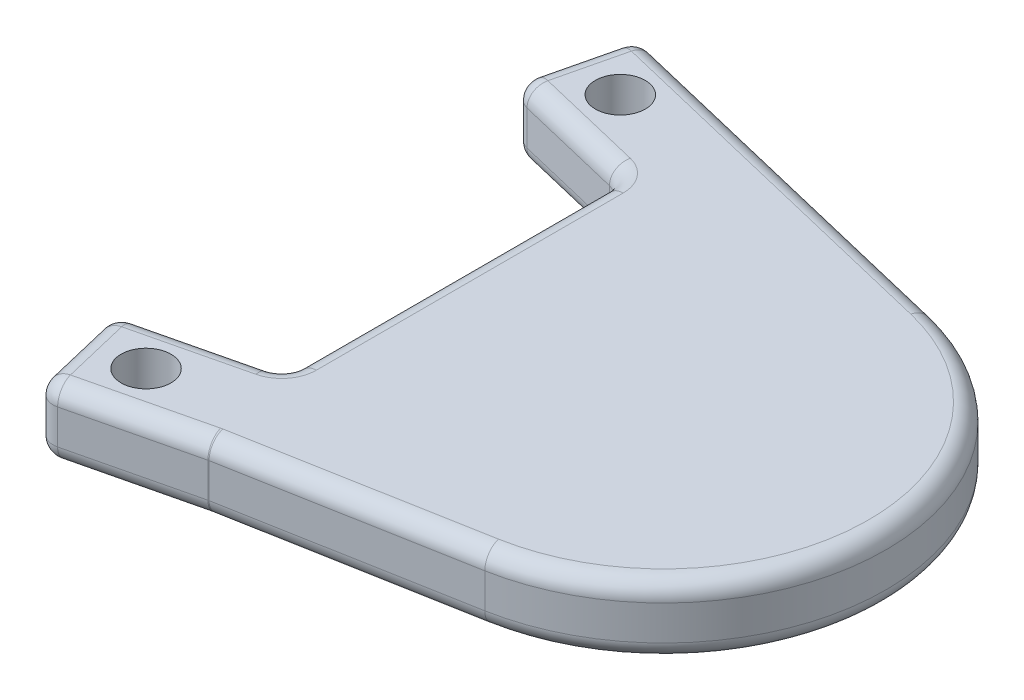
SolidWorks part; units mm, degrees
ref_plane "Front Plane" through (0, 0, 0) normal (0, 0, 1) x (1, 0, 0)
ref_plane "Top Plane" through (0, 0, 0) normal (0, 1, 0) x (1, 0, 0)
ref_plane "Right Plane" through (0, 0, 0) normal (1, 0, 0) x (0, 0, -1)
sketch "Sketch1" plane through (0, 0, 0) normal (0, 1, 0) x (1, 0, 0)
  line L0 (20.1768, -12.5857) -> (55.4095, -21.0327)
  line L7 (30.6561, -55.5343) -> (30.6561, -24.893)
  line L8 (30.6561, -24.893) -> (17.9561, -21.8482)
  line L9 (17.9561, -21.8482) -> (20.1768, -12.5857)
  line L11 (20.1768, -67.8416) -> (32.8768, -64.7968)
  line L12 (32.8768, -64.7968) -> (54.307, -60.8969)
  line L13 (30.6561, -55.5343) -> (17.9561, -58.5791)
  line L14 (-49.0101, -74.6341) -> (30.0474, -55.6802) construction
  line L15 (17.9561, -58.5791) -> (20.1768, -67.8416)
  line L16 (50.6586, -60.5337) -> (-49.8976, -84.6418) construction
  line L25 (30.6561, -54.9083) -> (30.6561, -25.519) construction
  line L26 (30.0474, -24.7471) -> (-49.0101, -5.7932) construction
  line L29 (-49.8976, 4.2145) -> (29.6773, -14.8634) construction
  arc A0 (54.307, -60.8969) -> (55.4095, -21.0327) centre (50.6586, -40.8487) ccw
  dimension "D1" = 12.7
  dimension "D3" = 12.7
extrude "Boss-Extrude1" add sketch "Sketch1" along normal blind 6.35
sketch "Sketch2" plane through (0, 6.35, 0) normal (0, 1, 0) x (1, 0, 0)
  line L0 (30.6561, -24.893) -> (30.6561, -55.5343) construction
  line L1 (20.1768, -67.8416) -> (32.8768, -64.7968) construction
  line L2 (24.3061, -61.9541) -> (25.4165, -66.5854) construction
  line L4 (24.3061, -61.9541) -> (23.1958, -57.3229) construction
  line L5 (30.6561, -55.5343) -> (17.9561, -58.5791) construction
  line L6 (24.3061, -18.4732) -> (23.1958, -23.1044) construction
  line L7 (17.9561, -21.8482) -> (30.6561, -24.893) construction
  line L8 (24.3061, -18.4732) -> (25.4165, -13.8419) construction
  line L9 (55.4095, -21.0327) -> (20.1768, -12.5857) construction
  line L10 (55.4095, -21.0327) -> (20.1768, -12.5857) construction
  circle A10 centre (24.3061, -61.9541) radius 2.286
  circle A11 centre (24.3061, -18.4732) radius 2.286
  dimension "D1" = 6.35
  dimension "D4" = 4.572
  dimension "D2" = 6.35
extrude "Cut-Extrude1" cut sketch "Sketch2" against normal through all
sketch "Sketch5" plane through (0, 0, 0) normal (0, -1, 0) x (1, 0, 0)
  line L0 (50.6586, 40.8432) -> (57.8976, 40.8432) construction
  line L1 (50.6586, 48.0877) -> (50.6586, 40.8432) construction
  circle A0 centre (50.6586, 40.8432) radius 2.286
  circle A1 centre (50.6586, 40.8487) radius 7.239 construction
  dimension "D1" = 4.572
extrude "Cut-Extrude2" cut sketch "Sketch5" against normal offset from surface (4.7625 mm away) 1.5875 contours A0 up to face at (24.3061, 6.35, 64.2401)
fillet "Fillet1" radius 1.5875 25 edges at (24.3061, 6.35, 23.3706) (24.3061, 0, 23.3706) (24.3061, 6.35, 57.0567) (24.3061, 0, 57.0567) (37.7931, 6.35, 16.8092) (71.0284, 6.35, 41.412) (37.7931, 0, 16.8092) (71.0284, 0, 41.412) (30.6561, 3.175, 24.893) (30.6561, 6.35, 40.2137) (30.6561, 3.175, 55.5343) (30.6561, 0, 40.2137) (20.1768, 3.175, 12.5857) (19.0665, 6.35, 17.217) (17.9561, 3.175, 21.8482) (19.0665, 0, 17.217) (43.5919, 6.35, 62.8469) (43.5919, 0, 62.8469) (26.5268, 6.35, 66.3192) (32.8768, 3.175, 64.7968) (26.5268, 0, 66.3192) (17.9561, 3.175, 58.5791) (19.0665, 6.35, 63.2103) (20.1768, 3.175, 67.8416) (19.0665, 0, 63.2103)
